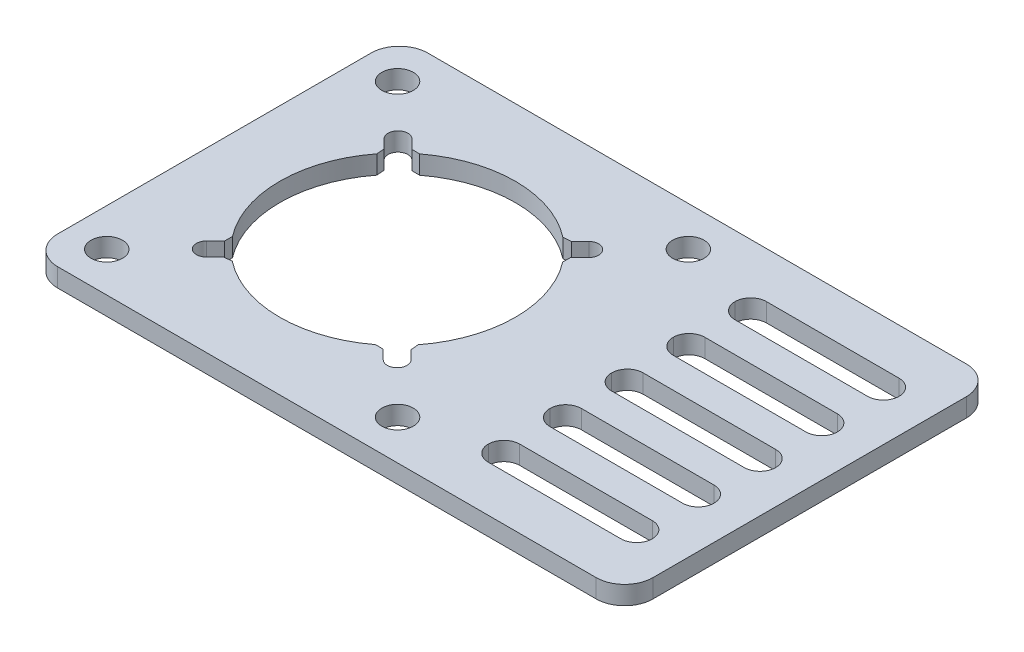
SolidWorks part; units mm, degrees
ref_plane "Front Plane" through (0, 0, 0) normal (0, 0, 1) x (1, 0, 0)
ref_plane "Top Plane" through (0, 0, 0) normal (0, 1, 0) x (1, 0, 0)
ref_plane "Right Plane" through (0, 0, 0) normal (1, 0, 0) x (0, 0, -1)
sketch "Sketch1" plane through (0, 0, 0) normal (0, 1, 0) x (1, 0, 0)
  line L1 (-48.25, 30) -> (48.25, 30)
  line L2 (-48.25, 30) -> (-48.25, -30)
  line L3 (-48.25, -30) -> (48.25, -30)
  line L4 (48.25, 30) -> (48.25, -30)
  line L5 (-48.25, 30) -> (48.25, -30) construction
  line L6 (-48.25, -30) -> (48.25, 30) construction
  point P0 (0, 0)
  dimension "D1" = 60
  dimension "D2" = 96.5
extrude "Boss-Extrude1" add sketch "Sketch1" along normal blind 3 contours L3 L4 L1 L2
sketch "Sketch2" plane through (0, 3, 0) normal (0, 1, 0) x (1, 0, 0)
  line L0 (-48.25, 30) -> (48.25, 30) construction
  line L1 (16.15, 17.45) -> (42.75, 17.45)
  line L2 (16.15, 17.45) -> (16.15, 22.55)
  line L3 (16.15, 22.55) -> (42.75, 22.55)
  line L4 (42.75, 17.45) -> (42.75, 22.55)
  line L21 (-48.25, 30) -> (-48.25, -30) construction
  line L22 (48.25, 30) -> (48.25, -30) construction
  line L23 (16.15, 7.45) -> (16.15, 12.55)
  line L24 (16.15, 7.45) -> (42.75, 7.45)
  line L25 (42.75, 7.45) -> (42.75, 12.55)
  line L26 (16.15, 12.55) -> (42.75, 12.55)
  line L27 (16.15, -2.55) -> (16.15, 2.55)
  line L28 (16.15, -2.55) -> (42.75, -2.55)
  line L29 (42.75, -2.55) -> (42.75, 2.55)
  line L30 (16.15, 2.55) -> (42.75, 2.55)
  line L31 (16.15, -12.55) -> (16.15, -7.45)
  line L32 (16.15, -12.55) -> (42.75, -12.55)
  line L33 (42.75, -12.55) -> (42.75, -7.45)
  line L34 (16.15, -7.45) -> (42.75, -7.45)
  line L35 (16.15, -22.55) -> (16.15, -17.45)
  line L36 (16.15, -22.55) -> (42.75, -22.55)
  line L37 (42.75, -22.55) -> (42.75, -17.45)
  line L38 (16.15, -17.45) -> (42.75, -17.45)
  line L39 (-5.5698, 15.1808) -> (-4.1447, 16.5996)
  line L40 (-18.55, 0) -> (-37.65, 0) construction
  line L41 (-18.55, 0) -> (-34.0158, 15.5342) construction
  line L42 (-33.7308, 12.9802) -> (-35.1496, 14.4053)
  line L43 (-32.8819, 16.663) -> (-31.4094, 15.184)
  line L44 (-33.628, 11.7245) -> (-33.7308, 12.9802)
  line L45 (-31.4094, 15.184) -> (-30.1405, 15.1812)
  line L46 (-6.8255, 15.078) -> (-5.5698, 15.1808)
  line L47 (-1.887, 14.3319) -> (-3.366, 12.8594)
  line L48 (-3.366, 12.8594) -> (-3.3688, 11.5905)
  line L49 (-3.3692, -12.9802) -> (-1.9504, -14.4053)
  line L50 (-3.472, -11.7245) -> (-3.3692, -12.9802)
  line L51 (-4.2181, -16.663) -> (-5.6906, -15.184)
  line L52 (-5.6906, -15.184) -> (-6.9595, -15.1812)
  line L53 (-31.5302, -15.1808) -> (-32.9553, -16.5996)
  line L54 (-30.2745, -15.078) -> (-31.5302, -15.1808)
  line L55 (-35.213, -14.3319) -> (-33.734, -12.8594)
  line L56 (-33.734, -12.8594) -> (-33.7312, -11.5905)
  arc A0 (-33.628, 11.7245) -> (-33.7312, -11.5905) centre (-18.55, 0) ccw
  circle A2 centre (-42.12, 23.57) radius 2.55
  circle A3 centre (5.02, 23.57) radius 2.55
  circle A4 centre (5.02, -23.57) radius 2.55
  circle A5 centre (-42.12, -23.57) radius 2.55
  arc A6 (-35.1496, 14.4053) -> (-32.8819, 16.663) centre (-34.0158, 15.5342) cw
  arc A7 (-4.1447, 16.5996) -> (-1.887, 14.3319) centre (-3.0158, 15.4658) cw
  arc A8 (-1.9504, -14.4053) -> (-4.2181, -16.663) centre (-3.0842, -15.5342) cw
  arc A9 (-32.9553, -16.5996) -> (-35.213, -14.3319) centre (-34.0842, -15.4658) cw
  arc A10 (-6.8255, 15.078) -> (-30.1405, 15.1812) centre (-18.55, 0) ccw
  arc A11 (-3.472, -11.7245) -> (-3.3688, 11.5905) centre (-18.55, 0) ccw
  arc A12 (-30.2745, -15.078) -> (-6.9595, -15.1812) centre (-18.55, 0) ccw
  point P38 (48.25, 0)
  point P69 (-18.55, 0)
  dimension "D3" = 38.2
  dimension "D4" = 5.1
  dimension "D18" = 1.6
  dimension "D1" = 5.1
  dimension "D2" = 26.6
  dimension "D5" = 6.43
  dimension "D6" = 6.13
  dimension "D9" = 47.14
  dimension "D10" = 47.14
  dimension "D11" = 7.45
  dimension "D12" = 5.5
  dimension "D14" = 10
  dimension "D15" = 29.7
  dimension "D16" = 45.126
  dimension "D17" = 21.9203
  dimension "D19" = 2.011
  dimension "D20" = 40.195
  dimension "D21" = 2.087
  dimension "D22" = 45
  dimension "D23" = 4
  dimension "D7" = 2
  dimension "D8" = 2
  dimension "D13" = 5
extrude "Cut-Extrude1" cut sketch "Sketch2" against normal through all
fillet "Fillet1" radius 2.55 20 edges at (42.75, 1.5, 12.55) (42.75, 1.5, 22.55) (42.75, 1.5, 17.45) (42.75, 1.5, 7.45) (42.75, 1.5, 2.55) (42.75, 1.5, -2.55) (42.75, 1.5, -7.45) (42.75, 1.5, -12.55) (42.75, 1.5, -17.45) (42.75, 1.5, -22.55) (16.15, 1.5, -17.45) (16.15, 1.5, -22.55) (16.15, 1.5, 22.55) (16.15, 1.5, 17.45) (16.15, 1.5, 12.55) (16.15, 1.5, 7.45) (16.15, 1.5, 2.55) (16.15, 1.5, -2.55) (16.15, 1.5, -7.45) (16.15, 1.5, -12.55)
fillet "Fillet2" radius 4.6 4 edges at (48.25, 1.5, -30) (48.25, 1.5, 30) (-48.25, 1.5, 30) (-48.25, 1.5, -30)
